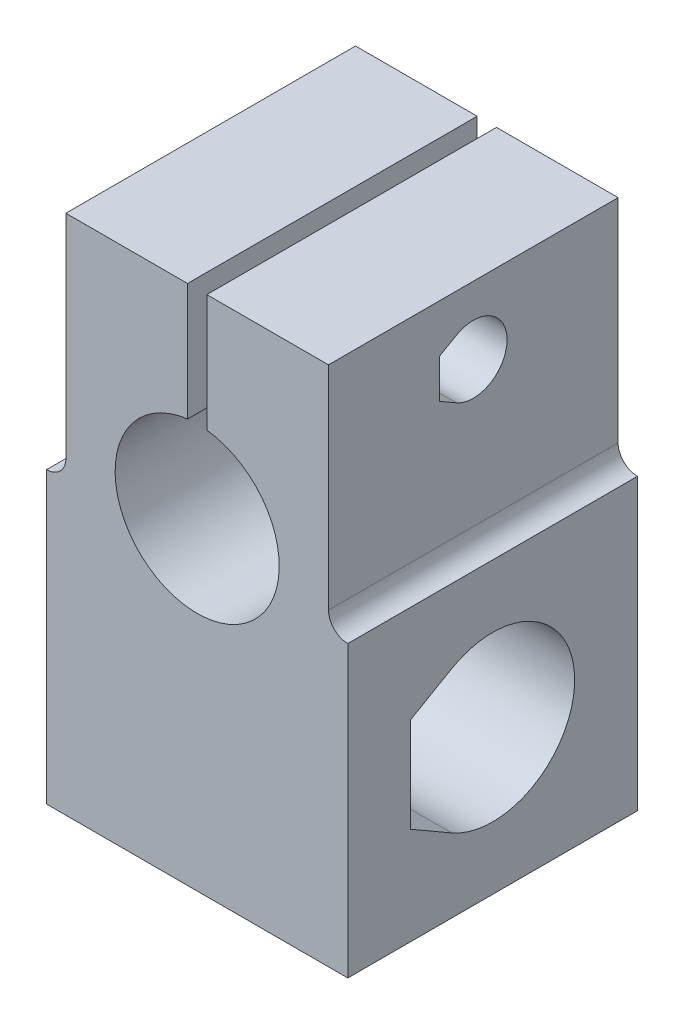
SolidWorks part; units mm, degrees
ref_plane "Piano frontale" through (0, 0, 0) normal (0, 0, 1) x (1, 0, 0)
ref_plane "Piano superiore" through (0, 0, 0) normal (0, 1, 0) x (1, 0, 0)
ref_plane "Piano destro" through (0, 0, 0) normal (1, 0, 0) x (0, 0, -1)
sketch "Schizzo1" plane through (0, 0, 0) normal (0, 0, 1) x (1, 0, 0)
  line L0 (-7.8, 0) -> (-7.8, 15)
  line L1 (-7.8, 15) -> (-6.8, 15)
  line L2 (-6.8, 15) -> (-6.8, 27)
  line L3 (-6.8, 27) -> (-0.5, 27)
  line L4 (-0.5, 27) -> (-0.5, 20.9205)
  line L5 (0.5, 27) -> (0.5, 20.9205)
  line L6 (0.5, 27) -> (6.8, 27)
  line L7 (6.8, 27) -> (6.8, 15)
  line L8 (6.8, 15) -> (7.8, 15)
  line L9 (7.8, 15) -> (7.8, 0)
  line L10 (7.8, 0) -> (-7.8, 0)
  line L11 (0, 0) -> (0, 37.7654) construction
  line L12 (-7.8, 7.5) -> (7.8, 7.5) construction
  arc A62 (-0.5, 20.9205) -> (0.5, 20.9205) centre (0, 16.7) ccw
  dimension "D3" = 8.5
  dimension "D5" = 12
  dimension "D8" = 9.2
  dimension "D1" = 15
  dimension "D2" = 1
  dimension "D6" = 15.6
  dimension "D7" = 1
extrude "Main body" add sketch "Schizzo1" along normal mid plane 15 contours L5 A62 L4 L3 L2 L1 L0 L10 L9 L8 L7 L6
sketch "Schizzo2" plane through (6.8, 0, 0) normal (1, 0, 0) x (0, 0, -1)
  line L0 (-7.5, 27) -> (7.5, 27) construction
  line L1 (-7.5, 27) -> (7.5, 27)
  line L2 (0, 27) -> (0, 23.5) construction
  line L3 (-1.75, 22.4896) -> (-1.75, 24.5104)
  line L4 (-1.75, 24.5104) -> (-0.875, 25.0155)
  line L5 (-1.75, 22.4896) -> (-0.875, 21.9845)
  arc A0 (-0.875, 21.9845) -> (-0.875, 25.0155) centre (0, 23.5) ccw
  point P9 (-1.75, 23.5)
  dimension "D1" = 3.5
  dimension "D2" = 120
  dimension "D3" = 3.5
extrude "Screw" cut sketch "Schizzo2" against normal through all both and the other way through all contours A0 L4 L3 L5
sketch "Schizzo6" plane through (-6.8, 0, 0) normal (-1, 0, 0) x (0, 0, 1)
  line L1 (3.25, 23.5) -> (1.625, 26.3146)
  line L2 (1.625, 26.3146) -> (-1.625, 26.3146)
  line L3 (-1.625, 26.3146) -> (-3.25, 23.5)
  line L4 (-3.25, 23.5) -> (-1.625, 20.6854)
  line L5 (-1.625, 20.6854) -> (1.625, 20.6854)
  line L6 (1.625, 20.6854) -> (3.25, 23.5)
  circle A0 centre (0, 23.5) radius 2.8146 construction
  dimension "D1" = 6.5
extrude "Nut recess" cut sketch "Schizzo6" against normal blind 2.4
sketch "Schizzo7" plane through (-7.8, 0, 0) normal (-1, 0, 0) x (0, 0, 1)
  line L0 (-7.5, 15) -> (7.5, 0) construction
  line L1 (4.25, 5.0463) -> (4.25, 9.9537)
  line L2 (4.25, 9.9537) -> (2.125, 11.1806)
  line L3 (4.25, 5.0463) -> (2.125, 3.8194)
  arc A0 (2.125, 11.1806) -> (2.125, 3.8194) centre (0, 7.5) ccw
  point P9 (4.25, 7.5)
  dimension "D1" = 8.5
extrude "Bar hole" cut sketch "Schizzo7" against normal through all
sketch "Schizzo8" plane through (0, 0, -7.5) normal (0, 0, -1) x (-1, 0, 0)
  line L0 (-3.3425, 15) -> (-3.8952, 15)
  line L1 (3.3425, 15) -> (3.8952, 15)
  line L20 (-6.8, 15) -> (6.8, 15) construction
  arc A0 (-0.5, 20.9205) -> (0.5, 20.9205) centre (0, 16.7) ccw construction
  arc A1 (-3.8952, 15) -> (3.8952, 15) centre (0, 16.7) ccw construction
  arc A2 (3.3425, 15) -> (-3.3425, 15) centre (0, 16.7) cw
  arc M12 (0.5, 20.9205) -> (-0.5, 20.9205) centre (0, 16.7) cw
  dimension "D1" = 3.75
extrude "Rod stop" add sketch "Schizzo8" against normal blind 1 contours M12 | M12 | M12 | M12 | M12 | M12 | M12 | M12 region at (0, 12.868, -7.5)
fillet "Relief 1" radius 1 1 edges at (6.8, 15, 0)
fillet "Relief 2" radius 1 1 edges at (-6.8, 15, 0)
ref_axis "Bar axis" through (7.8, 7.5, 0) along (-1, 0, 0)
ref_axis "Rod axis" through (0, 16.7, 7.5) along (0, 0, -1)
ref_axis "Rod clamp axis" through (0.5, 23.5, 0) along (1, 0, 0)
fillet "Raccordo2" radius 1 2 edges at (-3.8952, 15, -7) (3.8952, 15, -7)
